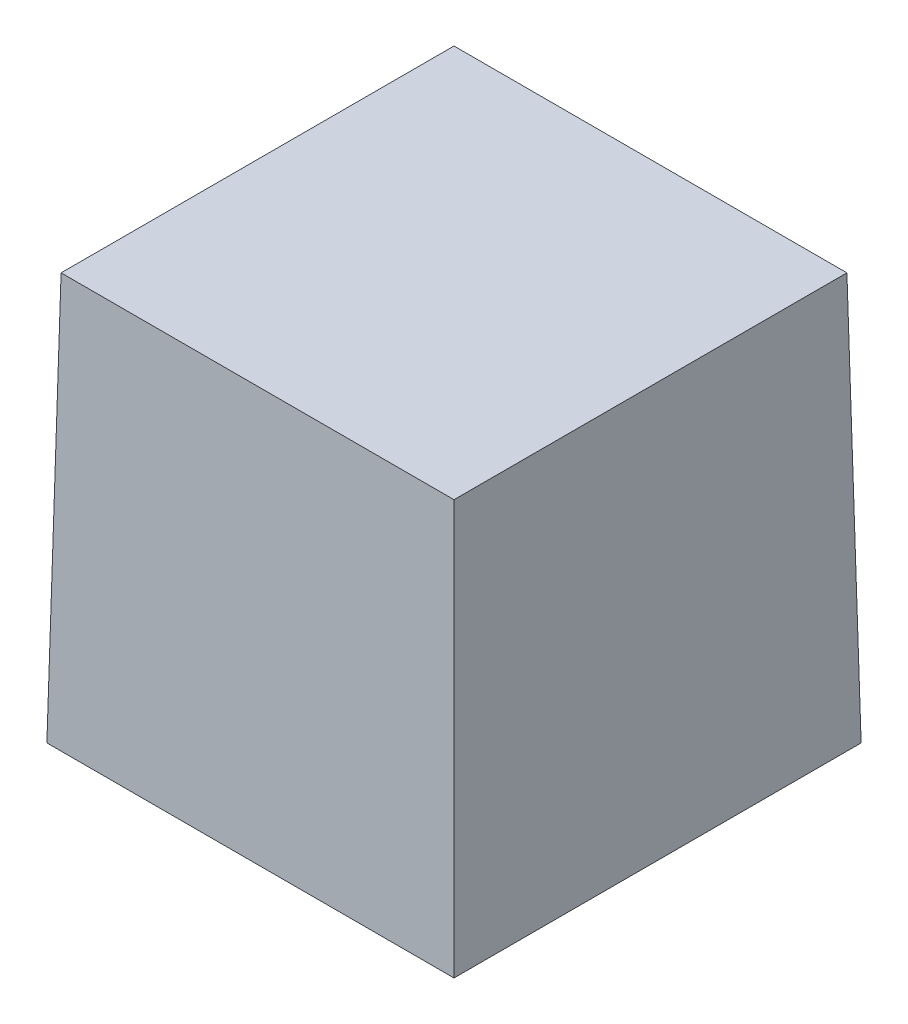
SolidWorks part; units mm, degrees
material "Liga 1060"
ref_plane "Plano frontal" through (0, 0, 0) normal (0, 0, 1) x (1, 0, 0)
ref_plane "Plano superior" through (0, 0, 0) normal (0, 1, 0) x (1, 0, 0)
ref_plane "Plano direito" through (0, 0, 0) normal (1, 0, 0) x (0, 0, -1)
sketch "Esboço1" plane through (0, 0, 0) normal (0, 1, 0) x (1, 0, 0)
  line L0 (0, 0) -> (30, 0)
  line L1 (30, 0) -> (30, 30)
  line L2 (30, 30) -> (0, 30)
  line L3 (0, 30) -> (0, 0)
  dimension "D1" = 30
  dimension "D2" = 30
extrude "Ressalto-extrusão1" add sketch "Esboço1" along normal blind 30 draft 1 contours L0 L1 L2 L3
